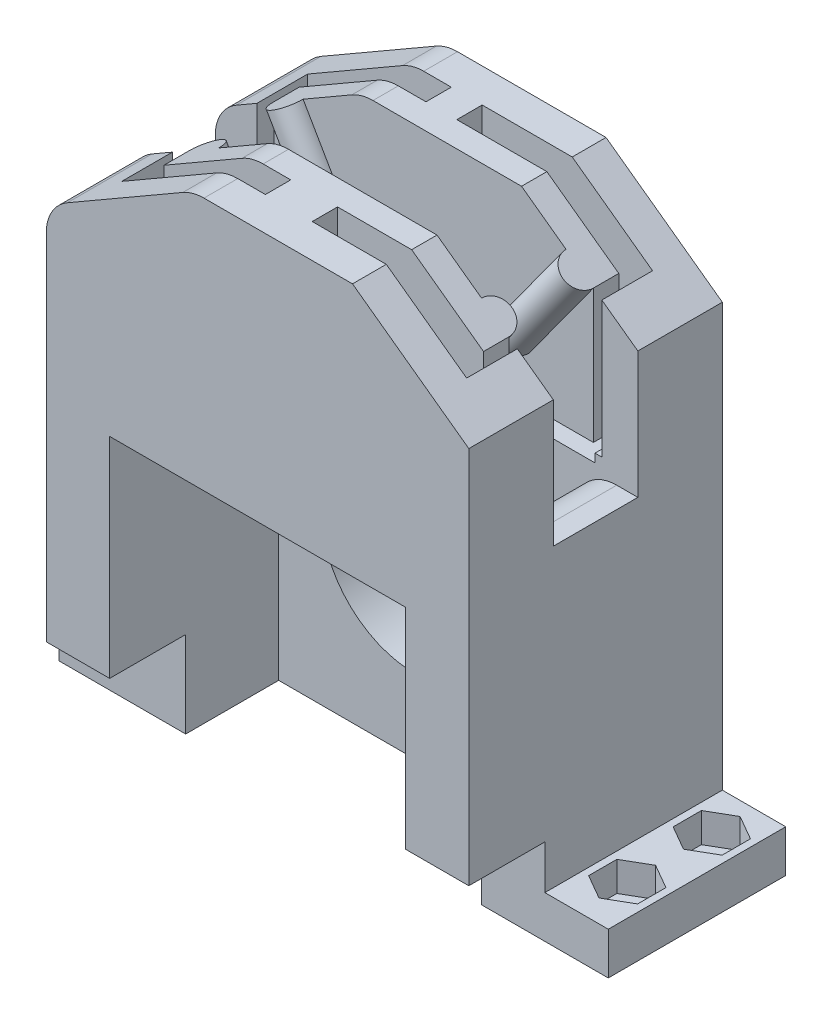
SolidWorks part; units mm, degrees
ref_plane "Front Plane" through (0, 0, 0) normal (0, 0, 1) x (1, 0, 0)
ref_plane "Top Plane" through (0, 0, 0) normal (0, 1, 0) x (1, 0, 0)
ref_plane "Right Plane" through (0, 0, 0) normal (1, 0, 0) x (0, 0, -1)
sketch "Sketch1" plane through (0, 0, 0) normal (0, 0, 1) x (1, 0, 0)
  line L0 (0.5834, 17.8723) -> (-16.7371, 7.8723)
  line L1 (-16.7371, 17.8723) -> (33.2629, 17.8723)
  line L2 (-16.7371, 17.8723) -> (-16.7371, -47.1277)
  line L3 (-16.7371, -47.1277) -> (33.2629, -47.1277)
  line L4 (33.2629, 17.8723) -> (33.2629, -47.1277)
  line L5 (19.4991, 17.8723) -> (33.2629, 7.8723)
  dimension "D1" = 50
  dimension "D2" = 65
  dimension "D3" = 0
  dimension "D4" = 0
  dimension "D5" = 60
  dimension "D6" = 0
  dimension "D7" = 0
  dimension "D8" = 54
  dimension "D9" = 10
  dimension "D10" = 10
extrude "Boss-Extrude1" add sketch "Sketch1" along normal blind 30 contours L5 L1 L0 L2 L3 L4 region at (8.347, -16.0926, 0)
sketch "Sketch2" plane through (0, 17.8723, 0) normal (0, 1, 0) x (1, 0, 0)
  line L0 (0.5834, 0) -> (19.4991, 0) construction
  line L1 (-16.7371, -10) -> (33.2629, -10)
  line L2 (-16.7371, -10) -> (-16.7371, -20)
  line L3 (-16.7371, -20) -> (33.2629, -20)
  line L4 (33.2629, -10) -> (33.2629, -20)
  line L5 (0.5834, -30) -> (19.4991, -30) construction
  line L6 (33.2629, -30) -> (33.2629, 0) construction
  line L7 (-16.7371, -30) -> (-16.7371, 0) construction
  dimension "D1" = 10
  dimension "D2" = 10
  dimension "D3" = 0
  dimension "D4" = 0
extrude "Cut-Extrude1" cut sketch "Sketch2" against normal blind 25
sketch "Sketch3" plane through (0, -47.1277, 0) normal (0, -1, 0) x (1, 0, 0)
  line L0 (-16.7371, 30) -> (33.2629, 30) construction
  line L1 (-9.2371, 20) -> (25.7629, 20)
  line L2 (-9.2371, 20) -> (-9.2371, 10)
  line L3 (-9.2371, 10) -> (25.7629, 10)
  line L4 (25.7629, 20) -> (25.7629, 10)
  line L5 (-16.7371, 0) -> (33.2629, 0) construction
  line L6 (33.2629, 30) -> (33.2629, 0) construction
  line L7 (-16.7371, 30) -> (-16.7371, 0) construction
  dimension "D1" = 10
  dimension "D2" = 10
  dimension "D3" = 7.5
  dimension "D4" = 7.5
sketch "Sketch4" plane through (-7.5931, 13.1516, 0) normal (-0.5, 0.866, 0) x (0, 0, 1)
  line L0 (10, -10.5586) -> (10, 9.4414) construction
  line L1 (10, -10.5586) -> (0, -10.5586) construction
  line L2 (20, 9.4414) -> (20, -10.5586) construction
  line L3 (30, -10.5586) -> (20, -10.5586) construction
  circle A0 centre (10, -0.5586) radius 2
  circle A1 centre (20, -0.5586) radius 2
  dimension "D2" = 10
  dimension "D4" = 4
  dimension "D5" = 4
  dimension "D6" = 10
  dimension "D1" = 0
  dimension "D3" = 0
extrude "Boss-Extrude2" add sketch "Sketch4" against normal blind 15
sketch "Sketch6" plane through (0, 17.8723, 0) normal (0, 1, 0) x (1, 0, 0)
  line L0 (19.4991, -10) -> (0.5834, -10) construction
  line L1 (-9.8089, -4) -> (5.1911, -4)
  line L2 (-9.8089, -4) -> (-9.8089, -7)
  line L3 (-9.8089, -7) -> (5.1911, -7)
  line L4 (5.1911, -4) -> (5.1911, -7)
  line L5 (-16.7371, -10) -> (-9.8089, -10) construction
  line L6 (-9.8089, -4) -> (-11.8089, -4)
  line L7 (-9.8089, -4) -> (-9.8089, -10)
  line L8 (-9.8089, -10) -> (-11.8089, -10)
  line L9 (-11.8089, -4) -> (-11.8089, -10)
  line L10 (-9.8089, -20) -> (-16.7371, -20) construction
  line L11 (-9.8089, -23) -> (5.1911, -23)
  line L12 (-9.8089, -23) -> (-9.8089, -26)
  line L13 (-9.8089, -26) -> (5.1911, -26)
  line L14 (5.1911, -23) -> (5.1911, -26)
  line L15 (-11.8089, -20) -> (-9.8089, -20)
  line L16 (-11.8089, -20) -> (-11.8089, -26)
  line L17 (-11.8089, -26) -> (-9.8089, -26)
  line L18 (-9.8089, -20) -> (-9.8089, -26)
  line L19 (0.5834, -20) -> (19.4991, -20) construction
  line M8 (0.5834, 0) -> (0.5834, -10)
  dimension "D1" = 0
  dimension "D2" = 3
  dimension "D3" = 15
  dimension "D4" = 3
  dimension "D5" = 0
  dimension "D6" = 0
  dimension "D7" = 2
  dimension "D8" = 0
  dimension "D9" = 0
  dimension "D10" = 0
  dimension "D11" = 2
  dimension "D12" = 0
  dimension "D13" = 0
  dimension "D14" = 3
  dimension "D15" = 3
  dimension "D16" = 15
extrude "Cut-Extrude15" cut sketch "Sketch6" against normal blind 24 contours L4 L1 L3 M8 | L2 L3 L1 M8 | L14 L11 L12 L13 | L18 L15 L16 L17 L12 | L9 L8 L7 L6 region at (-4.6127, 17.8723, 5.5) region at (2.8873, 17.8723, 5.5) region at (-2.3089, 17.8723, 24.5) region at (-10.8089, 17.8723, 23)
sketch "Sketch7" plane through (0, 0, 10) normal (0, 0, 1) x (1, 0, 0)
  line L0 (-9.8089, -6.1277) -> (-11.8089, -6.1277) construction
  line L1 (-9.8089, -4.1277) -> (28.1911, -4.1277)
  line L2 (-9.8089, -4.1277) -> (-9.8089, -6.1277)
  line L3 (-9.8089, -6.1277) -> (28.1911, -6.1277)
  line L4 (28.1911, -4.1277) -> (28.1911, -6.1277)
  line L6 (-9.8089, -6.1277) -> (-9.8089, 11.8723) construction
  dimension "D1" = 0
  dimension "D2" = 0
  dimension "D3" = 2
  dimension "D4" = 38
extrude "Cut-Extrude16" cut sketch "Sketch7" against normal blind 3 and the other way blind 13
sketch "Sketch8" plane through (0, 0, 30) normal (0, 0, 1) x (1, 0, 0)
  line L0 (-16.7371, -47.1277) -> (33.2629, -47.1277) construction
  line L1 (-9.2371, -12.1277) -> (25.7629, -12.1277)
  line L2 (-9.2371, -12.1277) -> (-9.2371, -47.1277)
  line L3 (-9.2371, -47.1277) -> (25.7629, -47.1277)
  line L4 (25.7629, -12.1277) -> (25.7629, -47.1277)
  line L5 (33.2629, 7.8723) -> (33.2629, -47.1277) construction
  line L6 (-16.7371, 7.8723) -> (-16.7371, -47.1277) construction
  point P6 (33.2629, -19.6277)
  dimension "D1" = 0
  dimension "D2" = 35
  dimension "D3" = 7.5
  dimension "D4" = 7.5
extrude "Cut-Extrude17" cut sketch "Sketch8" against normal up to surface (10 mm away) up to face at (3.9188, 3.5299, 20)
sketch "Sketch9" plane through (0, 0, 10) normal (0, 0, 1) x (1, 0, 0)
  line L1 (25.7629, -47.1277) -> (-9.2371, -47.1277) construction
  circle A0 centre (6.8891, -27.3277) radius 11.05
  dimension "D1" = 22.1
  dimension "D2" = 19.8
extrude "Cut-Extrude18" cut sketch "Sketch3" against normal up to surface (40 mm away) up to face at (8.2629, -7.1277, 15)
extrude "Cut-Extrude19" cut sketch "Sketch9" against normal blind 8
fillet "Fillet4" radius 5 1 edges at (25.7629, -7.1277, 15) type face fillet first side face at (29.5129, -7.1277, 15) second side face at (25.7629, -22.1277, 20)
fillet "Fillet5" radius 5 1 edges at (-16.7371, 7.8723, 5) type face fillet first side face at (-9.3208, 12.154, 4.6667) second side face at (-16.7371, -9.6277, 15)
fillet "Fillet6" radius 5 1 edges at (-16.7371, 7.8723, 25) type face fillet first side face at (-9.3208, 12.154, 25.3333) second side face at (-16.7371, -10.3494, 15)
fillet "Fillet7" radius 5 1 edges at (0.5834, 17.8723, 2) type face fillet first side face at (-8.4875, 12.6352, 4.6667) second side face at (6.1763, 17.8723, 5.25)
fillet "Fillet8" radius 5 1 edges at (0.5834, 17.8723, 8.5) type face fillet first side face at (-4.9591, 14.6723, 9.2) second side face at (6.5112, 17.8723, 5.25)
fillet "Fillet9" radius 5 1 edges at (0.5834, 17.8723, 21.5) type face fillet first side face at (-4.9591, 14.6723, 20.8) second side face at (6.4643, 17.8723, 24.75)
fillet "Fillet10" radius 5 1 edges at (0.5834, 17.8723, 28) type face fillet first side face at (-8.4875, 12.6352, 25.3333) second side face at (6.7992, 17.8723, 24.75)
sketch "Sketch10" plane through (33.2629, 0, 0) normal (1, 0, 0) x (0, 0, -1)
  line L0 (-30, -47.1277) -> (0, -47.1277) construction
  line L1 (-30, -36.9277) -> (-21, -36.9277)
  line L2 (-30, -36.9277) -> (-30, -47.1277)
  line L3 (-30, -47.1277) -> (-21, -47.1277)
  line L4 (-21, -36.9277) -> (-21, -47.1277)
  line L5 (-30, 7.8723) -> (-30, -47.1277) construction
  dimension "D1" = 0
  dimension "D2" = 0
  dimension "D3" = 9
  dimension "D4" = 10.2
extrude "Cut-Extrude20" cut sketch "Sketch10" against normal through all
sketch "Sketch11" plane through (15.2355, 20.9699, 0) normal (0.5878, 0.809, 0) x (0, 0, -1)
  line L0 (-20, -5.27) -> (-20, -22.2831) construction
  line L1 (-10, -22.2831) -> (-10, -5.27) construction
  line L2 (-10, -22.2831) -> (0, -22.2831) construction
  line L3 (-30, -22.2831) -> (-20, -22.2831) construction
  circle A0 centre (-20, -13.7831) radius 2
  circle A1 centre (-10, -13.7831) radius 2
  dimension "D2" = 4
  dimension "D4" = 4
  dimension "D6" = 8.5
  dimension "D1" = 0
  dimension "D3" = 0
  dimension "D5" = 8.5
extrude "Boss-Extrude3" add sketch "Sketch11" against normal blind 13
sketch "Sketch12" plane through (0, -7.1277, 0) normal (0, 1, 0) x (1, 0, 0)
  line L0 (-16.7371, -10) -> (-16.7371, -20) construction
  line L1 (-9.2371, -10) -> (-16.7371, -10)
  line L2 (-9.2371, -10) -> (-9.2371, -20)
  line L3 (-9.2371, -20) -> (-16.7371, -20)
  line L4 (-16.7371, -10) -> (-16.7371, -20)
  line L7 (-9.2371, -10) -> (-16.7371, -10) construction
  line L8 (-16.7371, -20) -> (-9.2371, -20) construction
  dimension "D1" = 0
  dimension "D3" = 0
  dimension "D4" = 0
extrude "Cut-Extrude21" cut sketch "Sketch12" against normal blind 3
fillet "Fillet11" radius 4 1 edges at (-9.2371, -10.1277, 15) type face fillet first side face at (-12.9871, -10.1277, 15) second side face at (-9.2371, -26.5777, 20.25)
sketch "Sketch13" plane through (0, 17.8723, 0) normal (0, 1, 0) x (1, 0, 0)
  line L1 (10.7303, -26) -> (28.0043, -26)
  line L2 (10.7303, -26) -> (10.7303, -23)
  line L3 (10.7303, -23) -> (28.0043, -23)
  line L4 (28.0043, -26) -> (28.0043, -23)
  line L5 (28.0043, -26) -> (29.0043, -26)
  line L6 (28.0043, -26) -> (28.0043, -16.4293)
  line L7 (28.0043, -16.4293) -> (29.0043, -16.4293)
  line L8 (29.0043, -26) -> (29.0043, -16.4293)
  line L9 (8.8426, -7) -> (28.0043, -7)
  line L10 (8.8426, -7) -> (8.8426, -4)
  line L11 (8.8426, -4) -> (28.0043, -4)
  line L12 (28.0043, -7) -> (28.0043, -4)
  line L13 (28.0043, -11.2788) -> (29.0043, -11.2788)
  line L14 (28.0043, -11.2788) -> (28.0043, -4)
  line L15 (28.0043, -4) -> (29.0043, -4)
  line L16 (29.0043, -11.2788) -> (29.0043, -4)
  line L17 (1.9232, -20) -> (19.4991, -20) construction
  line L18 (19.4991, -10) -> (1.9232, -10) construction
  line M4 (19.4991, -30) -> (19.4991, -20)
  dimension "D1" = 3
  dimension "D2" = 3
  dimension "D3" = 0
  dimension "D4" = 0
  dimension "D5" = 0
  dimension "D6" = 1
  dimension "D7" = 1
  dimension "D8" = 0
  dimension "D9" = 3
  dimension "D10" = 3
  dimension "D11" = 0
  dimension "D12" = 0
extrude "Cut-Extrude22" cut sketch "Sketch13" against normal blind 23 contours L3 L2 L1 M4 | L1 L4 L3 M4 | L5 L8 L7 L6 L4 | L13 L16 L15 L12 L14 | L9 L12 L11 L10 region at (15.1147, 17.8723, 24.5) region at (23.7517, 17.8723, 24.5) region at (28.5043, 17.8723, 21.2147) region at (18.4234, 17.8723, 5.5) region at (28.5043, 17.8723, 7.6394)
sketch "Sketch14" plane through (-16.7371, 0, 0) normal (-1, 0, 0) x (0, 0, 1)
  line L0 (21, -47.1277) -> (21, -36.9277) construction
  line L1 (0, -42.1277) -> (21, -42.1277)
  line L2 (0, -42.1277) -> (0, -47.1277)
  line L3 (0, -47.1277) -> (21, -47.1277)
  line L4 (21, -42.1277) -> (21, -47.1277)
  line L5 (21, -47.1277) -> (0, -47.1277) construction
  line L6 (0, 4.9855) -> (0, -47.1277) construction
  dimension "D1" = 5
  dimension "D2" = 0
  dimension "D3" = 0
  dimension "D4" = 0
extrude "Boss-Extrude4" add sketch "Sketch14" along normal blind 7.5
sketch "Sketch15" plane through (33.2629, 0, 0) normal (1, 0, 0) x (0, 0, -1)
  line L0 (-21, -47.1277) -> (-21, -36.9277) construction
  line L1 (-21, -42.1277) -> (0, -42.1277)
  line L2 (-21, -42.1277) -> (-21, -47.1277)
  line L3 (-21, -47.1277) -> (0, -47.1277)
  line L4 (0, -42.1277) -> (0, -47.1277)
  line L5 (-21, -47.1277) -> (0, -47.1277) construction
  line L6 (0, 7.8723) -> (0, -47.1277) construction
  dimension "D1" = 0
  dimension "D2" = 0
  dimension "D3" = 0
  dimension "D4" = 5
extrude "Boss-Extrude5" add sketch "Sketch15" along normal blind 7.5
sketch "Sketch16" plane through (0, -42.1277, 0) normal (0, 1, 0) x (1, 0, 0)
  line L0 (40.7629, 0) -> (40.7629, -21) construction
  line L1 (37.0129, -11.6514) -> (34.1129, -13.3257)
  line L2 (34.1129, -13.3257) -> (34.1129, -16.6743)
  line L3 (34.1129, -16.6743) -> (37.0129, -18.3486)
  line L4 (37.0129, -18.3486) -> (39.9129, -16.6743)
  line L5 (39.9129, -16.6743) -> (39.9129, -13.3257)
  line L6 (39.9129, -13.3257) -> (37.0129, -11.6514)
  line L7 (37.0129, -1.6514) -> (34.1129, -3.3257)
  line L8 (34.1129, -3.3257) -> (34.1129, -6.6743)
  line L9 (34.1129, -6.6743) -> (37.0129, -8.3486)
  line L10 (37.0129, -8.3486) -> (39.9129, -6.6743)
  line L11 (39.9129, -6.6743) -> (39.9129, -3.3257)
  line L12 (39.9129, -3.3257) -> (37.0129, -1.6514)
  line L13 (40.7629, 0) -> (33.2629, 0) construction
  circle A0 centre (37.0129, -15) radius 2.9 construction
  circle A1 centre (37.0129, -5) radius 2.9 construction
  dimension "D3" = 5.8
  dimension "D4" = 5.8
  dimension "D7" = 5
  dimension "D8" = 10
  dimension "D1" = 0
  dimension "D2" = 0
  dimension "D5" = 3.75
  dimension "D6" = 3.75
extrude "Cut-Extrude23" cut sketch "Sketch16" against normal blind 3.5
sketch "Sketch17" plane through (0, -45.6277, 0) normal (0, 1, 0) x (1, 0, 0)
  line L1 (40.7629, 0) -> (40.7629, -21) construction
  line L2 (40.7629, 0) -> (33.2629, 0) construction
  circle A0 centre (37.0129, -15) radius 1.425
  circle A1 centre (37.0129, -5) radius 1.425
  point P4 (37.0129, 0)
  dimension "D1" = 2.85
  dimension "D2" = 2.85
  dimension "D3" = 3.75
  dimension "D4" = 3.75
  dimension "D5" = 5
  dimension "D6" = 10
extrude "Cut-Extrude24" cut sketch "Sketch17" against normal through all
